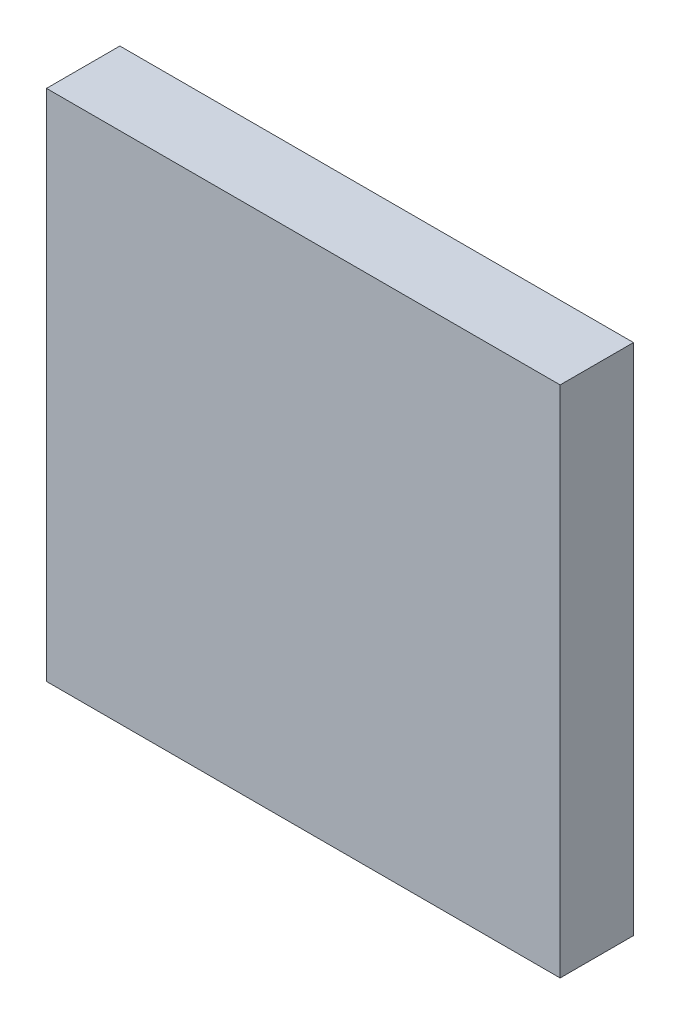
SolidWorks part; units mm, degrees
ref_plane "Спереди" through (0, 0, 0) normal (0, 0, 1) x (1, 0, 0)
ref_plane "Сверху" through (0, 0, 0) normal (0, 1, 0) x (1, 0, 0)
ref_plane "Справа" through (0, 0, 0) normal (1, 0, 0) x (0, 0, -1)
sketch "Эскиз5" plane through (0, 0, 0) normal (0, 0, 1) x (1, 0, 0)
  line L1 (-35, -35) -> (35, -35)
  line L2 (-35, -35) -> (-35, 35)
  line L3 (-35, 35) -> (35, 35)
  line L4 (35, -35) -> (35, 35)
  line L5 (-35, -35) -> (35, 35) construction
  line L6 (-35, 35) -> (35, -35) construction
  point P0 (0, 0)
extrude "Бобышка-Вытянуть2" add sketch "Эскиз5" along normal blind 10 contours L2 L3 L4 L1
sketch "Эскиз9" plane through (0, 0, 10) normal (0, 0, 1) x (1, 0, 0)
  line L0 (-15.9693, -2.4457) -> (-15.2752, -2.3914)
  line L1 (-14.1689, -1.194) -> (-14.17, 0.0011)
  line L2 (-15.1833, 1.1854) -> (-16.1735, 1.3414)
  line L3 (-7.5117, 15.2981) -> (-6.354, 13.3333)
  line L4 (-4.52, 14.0613) -> (-5.009, 16.2935)
  line L5 (5.8666, 15.0526) -> (5.5666, 14.4244)
  line L6 (6.0505, 12.8676) -> (7.0859, 12.271)
  line L7 (8.6182, 12.5564) -> (9.2484, 13.336)
  line L8 (16.9601, -1.13) -> (14.724, -1.1639)
  line L9 (14.4375, -3.1163) -> (16.5652, -3.7935)
  line L10 (10.1027, -12.6069) -> (9.7086, -12.0331)
  line L11 (8.1185, -11.6737) -> (7.0841, -12.2721)
  line L12 (6.5651, -13.7418) -> (6.9251, -14.6773)
  line L13 (-9.4469, -14.0923) -> (-8.37, -12.1694)
  line L14 (-9.9175, -10.9451) -> (-11.5447, -12.4356)
  line L15 (-30, -30) -> (30, -30)
  line L16 (30, -30) -> (30, 30)
  line L17 (30, 30) -> (-30, 30)
  line L18 (-30, 30) -> (-30, -30)
  ellipse E0 centre (-0.0001, 0.0435) end of major axis (-0.0001, 12.5436) minor radius 12.5001
  spline S0 degree 3 poles (3, -26) (3, -24.3431) (1.6569, -23) (0, -23) knots 0 0 0 0 0.2 0.2 0.2 0.2
  spline S1 degree 3 poles (0, -23) (-1.6568, -23) (-3, -24.3431) (-3, -26) knots 0.2 0.2 0.2 0.2 0.4 0.4 0.4 0.4
  spline S2 degree 3 poles (-3, -26) (-3, -27.6568) (-1.6569, -29) (0, -29) knots 0.4 0.4 0.4 0.4 0.6 0.6 0.6 0.6
  spline S3 degree 3 poles (0, -29) (1.6568, -29) (3, -27.6569) (3, -26) knots 0.6 0.6 0.6 0.6 1 1 1 1
  spline S4 degree 3 poles (-23, 0) (-23, 1.6569) (-24.3431, 3) (-26, 3) knots 0 0 0 0 0.2 0.2 0.2 0.2
  spline S5 degree 3 poles (-26, 3) (-27.6568, 3) (-29, 1.6569) (-29, 0) knots 0.2 0.2 0.2 0.2 0.4 0.4 0.4 0.4
  spline S6 degree 3 poles (-29, 0) (-29, -1.6568) (-27.6569, -3) (-26, -3) knots 0.4 0.4 0.4 0.4 0.6 0.6 0.6 0.6
  spline S7 degree 3 poles (-26, -3) (-24.3432, -3) (-23, -1.6569) (-23, 0) knots 0.6 0.6 0.6 0.6 1 1 1 1
  spline S8 degree 3 poles (29, 0) (29, 1.6569) (27.6569, 3) (26, 3) knots 0 0 0 0 0.2 0.2 0.2 0.2
  spline S9 degree 3 poles (26, 3) (24.3432, 3) (23, 1.6569) (23, 0) knots 0.2 0.2 0.2 0.2 0.4 0.4 0.4 0.4
  spline S10 degree 3 poles (23, 0) (23, -1.6568) (24.3431, -3) (26, -3) knots 0.4 0.4 0.4 0.4 0.6 0.6 0.6 0.6
  spline S11 degree 3 poles (26, -3) (27.6568, -3) (29, -1.6569) (29, 0) knots 0.6 0.6 0.6 0.6 1 1 1 1
  spline S12 degree 3 poles (3, 26) (3, 27.6569) (1.6569, 29) (0, 29) knots 0 0 0 0 0.2 0.2 0.2 0.2
  spline S13 degree 3 poles (0, 29) (-1.6568, 29) (-3, 27.6569) (-3, 26) knots 0.2 0.2 0.2 0.2 0.4 0.4 0.4 0.4
  spline S14 degree 3 poles (-3, 26) (-3, 24.3432) (-1.6569, 23) (0, 23) knots 0.4 0.4 0.4 0.4 0.6 0.6 0.6 0.6
  spline S15 degree 3 poles (0, 23) (1.6568, 23) (3, 24.3431) (3, 26) knots 0.6 0.6 0.6 0.6 1 1 1 1
  spline S16 degree 3 poles (-16.7485, -2.8866) (-16.7849, -2.7489) (-16.7119, -2.6575) (-16.5914, -2.5899) knots 0 0 0 0 0.021277 0.021277 0.021277 0.021277
  spline S17 degree 3 poles (-16.5914, -2.5899) (-16.4679, -2.5206) (-16.1105, -2.4568) (-15.9693, -2.4457) knots 0.021277 0.021277 0.021277 0.021277 0.042553 0.042553 0.042553 0.042553
  spline S18 degree 3 poles (-15.2752, -2.3914) (-14.6503, -2.3424) (-14.1684, -1.8208) (-14.1689, -1.194) knots 0.06383 0.06383 0.06383 0.06383 0.085106 0.085106 0.085106 0.085106
  spline S19 degree 3 poles (-14.17, 0.0011) (-14.1705, 0.5913) (-14.6002, 1.0936) (-15.1833, 1.1854) knots 0.106383 0.106383 0.106383 0.106383 0.12766 0.12766 0.12766 0.12766
  spline S20 degree 3 poles (-16.1735, 1.3414) (-16.4381, 1.383) (-16.9337, 1.6001) (-16.9034, 1.8662) knots 0.148936 0.148936 0.148936 0.148936 0.170213 0.170213 0.170213 0.170213
  spline S21 degree 3 poles (-16.9034, 1.8662) (-16.2735, 7.7755) (-12.6158, 12.7801) (-7.5117, 15.2981) knots 0.170213 0.170213 0.170213 0.170213 0.191489 0.191489 0.191489 0.191489
  spline S22 degree 3 poles (-6.354, 13.3333) (-6.1017, 12.914) (-5.5831, 12.7389) (-5.1282, 12.9194) knots 0.212766 0.212766 0.212766 0.212766 0.234043 0.234043 0.234043 0.234043
  spline S23 degree 3 poles (-5.1282, 12.9194) (-4.6734, 13.1) (-4.416, 13.5832) (-4.52, 14.0613) knots 0.234043 0.234043 0.234043 0.234043 0.255319 0.255319 0.255319 0.255319
  spline S24 degree 3 poles (-5.009, 16.2935) (-3.4256, 16.781) (-1.7434, 17.0434) (0, 17.0434) knots 0.276596 0.276596 0.276596 0.276596 0.297872 0.297872 0.297872 0.297872
  spline S25 degree 3 poles (0, 17.0434) (2.06, 17.0434) (4.0345, 16.6769) (5.8617, 16.0058) knots 0.297872 0.297872 0.297872 0.297872 0.319149 0.319149 0.319149 0.319149
  spline S26 degree 3 poles (5.8617, 16.0058) (5.9953, 15.9584) (6.0613, 15.8415) (6.1155, 15.7106) knots 0.319149 0.319149 0.319149 0.319149 0.340426 0.340426 0.340426 0.340426
  spline S27 degree 3 poles (6.1155, 15.7106) (6.1697, 15.5797) (5.9276, 15.1805) (5.8666, 15.0526) knots 0.340426 0.340426 0.340426 0.340426 0.361702 0.361702 0.361702 0.361702
  spline S28 degree 3 poles (5.5666, 14.4244) (5.2966, 13.8588) (5.5074, 13.1805) (6.0505, 12.8676) knots 0.382979 0.382979 0.382979 0.382979 0.404255 0.404255 0.404255 0.404255
  spline S29 degree 3 poles (7.0859, 12.271) (7.5974, 11.9764) (8.2472, 12.0974) (8.6182, 12.5564) knots 0.425532 0.425532 0.425532 0.425532 0.446809 0.446809 0.446809 0.446809
  spline S30 degree 3 poles (9.2484, 13.336) (9.4155, 13.5426) (9.7733, 13.9496) (9.9892, 13.8005) knots 0.468085 0.468085 0.468085 0.468085 0.489362 0.489362 0.489362 0.489362
  spline S31 degree 3 poles (9.9892, 13.8005) (9.9897, 13.8002) (9.9901, 13.7998) (9.9906, 13.7995) knots 0.489362 0.489362 0.489362 0.489362 0.510638 0.510638 0.510638 0.510638
  spline S32 degree 3 poles (9.9906, 13.7995) (14.2385, 10.7091) (17, 5.6988) (17, 0.0434) knots 0.510638 0.510638 0.510638 0.510638 0.531915 0.531915 0.531915 0.531915
  spline S33 degree 3 poles (17, 0.0434) (17, -0.351) (16.9865, -0.7423) (16.9601, -1.13) knots 0.531915 0.531915 0.531915 0.531915 0.553191 0.553191 0.553191 0.553191
  spline S34 degree 3 poles (14.724, -1.1639) (14.2347, -1.1728) (13.8237, -1.5344) (13.7527, -2.0186) knots 0.574468 0.574468 0.574468 0.574468 0.595745 0.595745 0.595745 0.595745
  spline S35 degree 3 poles (13.7527, -2.0186) (13.6816, -2.5027) (13.9714, -2.9672) (14.4375, -3.1163) knots 0.595745 0.595745 0.595745 0.595745 0.617021 0.617021 0.617021 0.617021
  spline S36 degree 3 poles (16.5652, -3.7935) (15.7442, -7.3523) (13.8058, -10.484) (11.1395, -12.7989) knots 0.638298 0.638298 0.638298 0.638298 0.659574 0.659574 0.659574 0.659574
  spline S37 degree 3 poles (11.1395, -12.7989) (11.0317, -12.8908) (10.5897, -12.8381) (10.4494, -12.8196) knots 0.659574 0.659574 0.659574 0.659574 0.680851 0.680851 0.680851 0.680851
  spline S38 degree 3 poles (10.4494, -12.8196) (10.3089, -12.8011) (10.1829, -12.7237) (10.1027, -12.6069) knots 0.680851 0.680851 0.680851 0.680851 0.702128 0.702128 0.702128 0.702128
  spline S39 degree 3 poles (9.7086, -12.0331) (9.3538, -11.5163) (8.661, -11.3598) (8.1185, -11.6737) knots 0.723404 0.723404 0.723404 0.723404 0.744681 0.744681 0.744681 0.744681
  spline S40 degree 3 poles (7.0841, -12.2721) (6.5732, -12.5677) (6.3531, -13.1909) (6.5651, -13.7418) knots 0.765957 0.765957 0.765957 0.765957 0.787234 0.787234 0.787234 0.787234
  spline S41 degree 3 poles (6.9251, -14.6773) (7.021, -14.9265) (6.922, -15.4856) (6.6778, -15.5949) knots 0.808511 0.808511 0.808511 0.808511 0.829787 0.829787 0.829787 0.829787
  spline S42 degree 3 poles (6.6778, -15.5949) (4.6278, -16.4714) (2.3705, -16.9566) (0, -16.9566) knots 0.829787 0.829787 0.829787 0.829787 0.851064 0.851064 0.851064 0.851064
  spline S43 degree 3 poles (0, -16.9566) (-3.4958, -16.9566) (-6.7452, -15.9014) (-9.4469, -14.0923) knots 0.851064 0.851064 0.851064 0.851064 0.87234 0.87234 0.87234 0.87234
  spline S44 degree 3 poles (-8.37, -12.1694) (-8.133, -11.7413) (-8.2407, -11.2045) (-8.6244, -10.9009) knots 0.893617 0.893617 0.893617 0.893617 0.914894 0.914894 0.914894 0.914894
  spline S45 degree 3 poles (-8.6244, -10.9009) (-9.0082, -10.5972) (-9.5554, -10.6159) (-9.9175, -10.9451) knots 0.914894 0.914894 0.914894 0.914894 0.93617 0.93617 0.93617 0.93617
  spline S46 degree 3 poles (-11.5447, -12.4356) (-14.22, -9.9595) (-16.0977, -6.6335) (-16.7485, -2.8866) knots 0.957447 0.957447 0.957447 0.957447 1 1 1 1
sketch "Эскиз13" plane through (0, 0, 10) normal (0, 0, 1) x (1, 0, 0)
  line L0 (-8.5, 3.8388) -> (-8.5, -2.9703)
  line L1 (8.5, -2.9278) -> (8.5, 3.8388)
  spline S0 degree 3 poles (-3.7602, -6.2881) (-4.1456, -5.7125) (-4.7609, -5.3316) (-5.448, -5.2431) knots 0 0 0 0 0.333333 0.333333 0.333333 0.333333
  spline S1 degree 3 poles (-5.448, -5.2431) (-6.135, -5.1547) (-6.8268, -5.3675) (-7.3454, -5.8267) knots 0.333333 0.333333 0.333333 0.333333 1 1 1 1
  spline S2 degree 3 poles (-8.2703, 4.2595) (-8.4134, 4.1675) (-8.5, 4.009) (-8.5, 3.8388) knots 0 0 0 0 1 1 1 1
  spline S3 degree 3 poles (8.2703, 4.2595) (3.2319, 7.4966) (-3.2319, 7.4966) (-8.2703, 4.2595) knots 0 0 0 0 1 1 1 1
  spline S4 degree 3 poles (8.5, 3.8388) (8.5, 4.009) (8.4134, 4.1675) (8.2703, 4.2595) knots 0 0 0 0 1 1 1 1
  spline S5 degree 3 poles (-8.9672, -4.0581) (-8.6689, -3.7749) (-8.5, -3.3816) (-8.5, -2.9703) knots 0 0 0 0 1 1 1 1
  spline S6 degree 3 poles (-8.9672, -4.0581) (-9.4419, -4.5088) (-9.4678, -5.2568) (-9.0253, -5.7393) knots 0 0 0 0 0.333333 0.333333 0.333333 0.333333
  spline S7 degree 3 poles (-9.0253, -5.7393) (-8.5829, -6.2218) (-7.8355, -6.2607) (-7.3454, -5.8267) knots 0.333333 0.333333 0.333333 0.333333 1 1 1 1
  spline S8 degree 3 poles (8.5, -2.9278) (8.5, -3.3579) (8.6732, -3.77) (8.9805, -4.0709) knots 0 0 0 0 1 1 1 1
  spline S9 degree 3 poles (7.6987, -6.0438) (6.4648, -5.5547) (5.0779, -5.6352) (3.9089, -6.2639) knots 0 0 0 0 1 1 1 1
  spline S10 degree 3 poles (7.6987, -6.0438) (8.2299, -6.2544) (8.8358, -6.0612) (9.1472, -5.5821) knots 0 0 0 0 0.333333 0.333333 0.333333 0.333333
  spline S11 degree 3 poles (9.1472, -5.5821) (9.4585, -5.1029) (9.3888, -4.4707) (8.9805, -4.0709) knots 0.333333 0.333333 0.333333 0.333333 1 1 1 1
  spline S12 degree 3 poles (3.1792, -6.3186) (1.2825, -5.6394) (-0.8063, -5.741) (-2.6281, -6.6012) knots 0 0 0 0 1 1 1 1
  spline S13 degree 3 poles (-3.7602, -6.2881) (-3.5123, -6.6582) (-3.0309, -6.7914) (-2.6281, -6.6012) knots 0 0 0 0 1 1 1 1
  spline S14 degree 3 poles (3.1792, -6.3186) (3.4192, -6.4045) (3.6844, -6.3847) (3.9089, -6.2639) knots 0 0 0 0 1 1 1 1
sketch "Эскиз15" plane through (0, 0, 10) normal (0, 0, 1) x (1, 0, 0)
  line L0 (-8.5, 3.8389) -> (-8.5, -2.9702)
  line L1 (8.5, -2.9277) -> (8.5, 3.8389)
  line L2 (-12.5, -12.5) -> (12.5, -12.5)
  line L3 (12.5, -12.5) -> (12.5, 12.5)
  line L4 (12.5, 12.5) -> (-12.5, 12.5)
  line L5 (-12.5, 12.5) -> (-12.5, -12.5)
  spline S0 degree 3 poles (8, 2.6874) (8, 2.9636) (7.7761, 3.1874) (7.5, 3.1874) knots 0 0 0 0 0.2 0.2 0.2 0.2
  spline S1 degree 3 poles (7.5, 3.1874) (7.2239, 3.1874) (7, 2.9636) (7, 2.6874) knots 0.2 0.2 0.2 0.2 0.4 0.4 0.4 0.4
  spline S2 degree 3 poles (7, 2.6874) (7, 2.4113) (7.2239, 2.1874) (7.5, 2.1874) knots 0.4 0.4 0.4 0.4 0.6 0.6 0.6 0.6
  spline S3 degree 3 poles (7.5, 2.1874) (7.7761, 2.1874) (8, 2.4113) (8, 2.6874) knots 0.6 0.6 0.6 0.6 1 1 1 1
  spline S4 degree 3 poles (-4.6079, 1.1218) (-4.6079, 1.6188) (-5.0108, 2.0218) (-5.5079, 2.0218) knots 0 0 0 0 0.2 0.2 0.2 0.2
  spline S5 degree 3 poles (-5.5079, 2.0218) (-6.0049, 2.0218) (-6.4079, 1.6188) (-6.4079, 1.1218) knots 0.2 0.2 0.2 0.2 0.4 0.4 0.4 0.4
  spline S6 degree 3 poles (-6.4079, 1.1218) (-6.4079, 0.6247) (-6.0049, 0.2218) (-5.5079, 0.2218) knots 0.4 0.4 0.4 0.4 0.6 0.6 0.6 0.6
  spline S7 degree 3 poles (-5.5079, 0.2218) (-5.0108, 0.2218) (-4.6079, 0.6247) (-4.6079, 1.1218) knots 0.6 0.6 0.6 0.6 1 1 1 1
  spline S8 degree 3 poles (7.0549, -0.2908) (7.0549, 0.2063) (6.652, 0.6092) (6.1549, 0.6092) knots 0 0 0 0 0.2 0.2 0.2 0.2
  spline S9 degree 3 poles (6.1549, 0.6092) (5.6579, 0.6092) (5.2549, 0.2063) (5.2549, -0.2908) knots 0.2 0.2 0.2 0.2 0.4 0.4 0.4 0.4
  spline S10 degree 3 poles (5.2549, -0.2908) (5.2549, -0.7878) (5.6579, -1.1908) (6.1549, -1.1908) knots 0.4 0.4 0.4 0.4 0.6 0.6 0.6 0.6
  spline S11 degree 3 poles (6.1549, -1.1908) (6.652, -1.1908) (7.0549, -0.7878) (7.0549, -0.2908) knots 0.6 0.6 0.6 0.6 1 1 1 1
  spline S12 degree 3 poles (-7, 2.6874) (-7, 2.9636) (-7.2239, 3.1874) (-7.5, 3.1874) knots 0 0 0 0 0.2 0.2 0.2 0.2
  spline S13 degree 3 poles (-7.5, 3.1874) (-7.7761, 3.1874) (-8, 2.9636) (-8, 2.6874) knots 0.2 0.2 0.2 0.2 0.4 0.4 0.4 0.4
  spline S14 degree 3 poles (-8, 2.6874) (-8, 2.4113) (-7.7761, 2.1874) (-7.5, 2.1874) knots 0.4 0.4 0.4 0.4 0.6 0.6 0.6 0.6
  spline S15 degree 3 poles (-7.5, 2.1874) (-7.2239, 2.1874) (-7, 2.4113) (-7, 2.6874) knots 0.6 0.6 0.6 0.6 1 1 1 1
  spline S16 degree 3 poles (-7.5909, -4.9282) (-7.5909, -4.6244) (-7.8371, -4.3782) (-8.1409, -4.3782) knots 0 0 0 0 0.2 0.2 0.2 0.2
  spline S17 degree 3 poles (-8.1409, -4.3782) (-8.4447, -4.3782) (-8.6909, -4.6244) (-8.6909, -4.9282) knots 0.2 0.2 0.2 0.2 0.4 0.4 0.4 0.4
  spline S18 degree 3 poles (-8.6909, -4.9282) (-8.6909, -5.2319) (-8.4447, -5.4782) (-8.1409, -5.4782) knots 0.4 0.4 0.4 0.4 0.6 0.6 0.6 0.6
  spline S19 degree 3 poles (-8.1409, -5.4782) (-7.8371, -5.4782) (-7.5909, -5.2319) (-7.5909, -4.9282) knots 0.6 0.6 0.6 0.6 1 1 1 1
  spline S20 degree 3 poles (8.6909, -4.9282) (8.6909, -4.6244) (8.4447, -4.3782) (8.1409, -4.3782) knots 0 0 0 0 0.2 0.2 0.2 0.2
  spline S21 degree 3 poles (8.1409, -4.3782) (7.8371, -4.3782) (7.5909, -4.6244) (7.5909, -4.9282) knots 0.2 0.2 0.2 0.2 0.4 0.4 0.4 0.4
  spline S22 degree 3 poles (7.5909, -4.9282) (7.5909, -5.2319) (7.8371, -5.4782) (8.1409, -5.4782) knots 0.4 0.4 0.4 0.4 0.6 0.6 0.6 0.6
  spline S23 degree 3 poles (8.1409, -5.4782) (8.4447, -5.4782) (8.6909, -5.2319) (8.6909, -4.9282) knots 0.6 0.6 0.6 0.6 1 1 1 1
  spline S24 degree 3 poles (3.9826, -5.4712) (3.9826, -5.195) (3.7587, -4.9712) (3.4826, -4.9712) knots 0 0 0 0 0.2 0.2 0.2 0.2
  spline S25 degree 3 poles (3.4826, -4.9712) (3.2064, -4.9712) (2.9826, -5.195) (2.9826, -5.4712) knots 0.2 0.2 0.2 0.2 0.4 0.4 0.4 0.4
  spline S26 degree 3 poles (2.9826, -5.4712) (2.9826, -5.7473) (3.2064, -5.9712) (3.4826, -5.9712) knots 0.4 0.4 0.4 0.4 0.6 0.6 0.6 0.6
  spline S27 degree 3 poles (3.4826, -5.9712) (3.7587, -5.9712) (3.9826, -5.7473) (3.9826, -5.4712) knots 0.6 0.6 0.6 0.6 1 1 1 1
  spline S28 degree 3 poles (-2.5123, -5.7872) (-2.5123, -5.5111) (-2.7362, -5.2872) (-3.0123, -5.2872) knots 0 0 0 0 0.2 0.2 0.2 0.2
  spline S29 degree 3 poles (-3.0123, -5.2872) (-3.2885, -5.2872) (-3.5123, -5.5111) (-3.5123, -5.7872) knots 0.2 0.2 0.2 0.2 0.4 0.4 0.4 0.4
  spline S30 degree 3 poles (-3.5123, -5.7872) (-3.5123, -6.0634) (-3.2885, -6.2872) (-3.0123, -6.2872) knots 0.4 0.4 0.4 0.4 0.6 0.6 0.6 0.6
  spline S31 degree 3 poles (-3.0123, -6.2872) (-2.7362, -6.2872) (-2.5123, -6.0634) (-2.5123, -5.7872) knots 0.6 0.6 0.6 0.6 1 1 1 1
  spline S32 degree 3 poles (6.6049, -0.2908) (6.6049, -0.0422) (6.4034, 0.1592) (6.1549, 0.1592) knots 0 0 0 0 0.2 0.2 0.2 0.2
  spline S33 degree 3 poles (6.1549, 0.1592) (5.9064, 0.1592) (5.7049, -0.0422) (5.7049, -0.2908) knots 0.2 0.2 0.2 0.2 0.4 0.4 0.4 0.4
  spline S34 degree 3 poles (5.7049, -0.2908) (5.7049, -0.5393) (5.9064, -0.7408) (6.1549, -0.7408) knots 0.4 0.4 0.4 0.4 0.6 0.6 0.6 0.6
  spline S35 degree 3 poles (6.1549, -0.7408) (6.4034, -0.7408) (6.6049, -0.5393) (6.6049, -0.2908) knots 0.6 0.6 0.6 0.6 1 1 1 1
  spline S36 degree 3 poles (-5.0579, 1.1218) (-5.0579, 1.3703) (-5.2594, 1.5718) (-5.5079, 1.5718) knots 0 0 0 0 0.2 0.2 0.2 0.2
  spline S37 degree 3 poles (-5.5079, 1.5718) (-5.7564, 1.5718) (-5.9579, 1.3703) (-5.9579, 1.1218) knots 0.2 0.2 0.2 0.2 0.4 0.4 0.4 0.4
  spline S38 degree 3 poles (-5.9579, 1.1218) (-5.9579, 0.8733) (-5.7564, 0.6718) (-5.5079, 0.6718) knots 0.4 0.4 0.4 0.4 0.6 0.6 0.6 0.6
  spline S39 degree 3 poles (-5.5079, 0.6718) (-5.2594, 0.6718) (-5.0579, 0.8733) (-5.0579, 1.1218) knots 0.6 0.6 0.6 0.6 1 1 1 1
  spline S40 degree 3 poles (5.7898, -5.6368) (5.8728, -5.6949) (5.9715, -5.7264) (6.0728, -5.7271) knots 0 0 0 0 1 1 1 1
  spline S41 degree 3 poles (-5.4083, -5.2485) (-5.2964, -5.2648) (-5.1822, -5.2427) (-5.0845, -5.1857) knots 0 0 0 0 1 1 1 1
  spline S42 degree 3 poles (-3.7602, -6.288) (-4.1456, -5.7124) (-4.7609, -5.3315) (-5.448, -5.243) knots 0 0 0 0 0.333333 0.333333 0.333333 0.333333
  spline S43 degree 3 poles (-5.448, -5.243) (-6.135, -5.1546) (-6.8268, -5.3674) (-7.3454, -5.8266) knots 0.333333 0.333333 0.333333 0.333333 1 1 1 1
  spline S44 degree 3 poles (-8.2703, 4.2596) (-8.4134, 4.1676) (-8.5, 4.0091) (-8.5, 3.8389) knots 0 0 0 0 1 1 1 1
  spline S45 degree 3 poles (8.2703, 4.2596) (3.2319, 7.4967) (-3.2319, 7.4967) (-8.2703, 4.2596) knots 0 0 0 0 1 1 1 1
  spline S46 degree 3 poles (8.5, 3.8389) (8.5, 4.0091) (8.4134, 4.1676) (8.2703, 4.2596) knots 0 0 0 0 1 1 1 1
  spline S47 degree 3 poles (5.7898, -5.6368) (2.563, -3.3793) (-1.6818, -3.2032) (-5.0845, -5.1857) knots 0 0 0 0 1 1 1 1
  spline S48 degree 3 poles (-8.9672, -4.058) (-8.6689, -3.7748) (-8.5, -3.3815) (-8.5, -2.9702) knots 0 0 0 0 1 1 1 1
  spline S49 degree 3 poles (-8.9672, -4.058) (-9.4419, -4.5087) (-9.4678, -5.2567) (-9.0253, -5.7392) knots 0 0 0 0 0.333333 0.333333 0.333333 0.333333
  spline S50 degree 3 poles (-9.0253, -5.7392) (-8.5829, -6.2217) (-7.8355, -6.2606) (-7.3454, -5.8266) knots 0.333333 0.333333 0.333333 0.333333 1 1 1 1
  spline S51 degree 3 poles (8.5, -2.9277) (8.5, -3.3578) (8.6732, -3.7699) (8.9805, -4.0708) knots 0 0 0 0 1 1 1 1
  spline S52 degree 3 poles (7.6987, -6.0437) (6.4648, -5.5546) (5.0779, -5.6351) (3.9089, -6.2638) knots 0 0 0 0 1 1 1 1
  spline S53 degree 3 poles (7.6987, -6.0437) (8.2299, -6.2543) (8.8358, -6.0611) (9.1472, -5.582) knots 0 0 0 0 0.333333 0.333333 0.333333 0.333333
  spline S54 degree 3 poles (9.1472, -5.582) (9.4585, -5.1028) (9.3888, -4.4706) (8.9805, -4.0708) knots 0.333333 0.333333 0.333333 0.333333 1 1 1 1
  spline S55 degree 3 poles (3.1792, -6.3185) (1.2825, -5.6393) (-0.8063, -5.7409) (-2.6281, -6.6011) knots 0 0 0 0 1 1 1 1
  spline S56 degree 3 poles (-3.7602, -6.288) (-3.5123, -6.6581) (-3.0309, -6.7913) (-2.6281, -6.6011) knots 0 0 0 0 1 1 1 1
  spline S57 degree 3 poles (3.1792, -6.3185) (3.4192, -6.4044) (3.6844, -6.3846) (3.9089, -6.2638) knots 0 0 0 0 1 1 1 1
sketch "обнижение под перлаж" plane through (0, 0, 10) normal (0, 0, 1) x (1, 0, 0)
  ellipse E0 centre (0, -7.2674) end of major axis (6.1105, -7.2674) minor radius 3.5988
sketch "Платина" plane through (0, 0, 10) normal (0, 0, 1) x (1, 0, 0)
  line L0 (12.3202, 9.8119) -> (12.2227, 9.9331)
  line L1 (2.5, -10.2511) -> (2.5, -15.1183)
  line L2 (7.4454, 12.0481) -> (8.1376, 12.9446)
  line L3 (11.9295, 9) -> (9.0138, 9)
  line L4 (8.1828, -12.8608) -> (5.8429, -9.208)
  line L5 (6.6238, -9) -> (11.9295, -9)
  line L6 (2.5, 15.1183) -> (2.5, 13.3766)
  line L7 (-0.6426, 13.86) -> (0.5426, 13.86)
  line L8 (1.1426, 14.46) -> (1.1426, 15.1613)
  line L9 (-6.3695, 9.5643) -> (-6.5795, 9.5485)
  line L10 (-0.9887, -9.3998) -> (-1.9416, -7.3197)
  line L11 (-0.0126, 4.7745) -> (-0.0058, 4.7671)
  line L12 (-5.5717, -10.8712) -> (-5.5074, -10.8831)
  line L13 (-2.7325, 15.5111) -> (-2.8513, 15.4898)
  line L14 (-1.1426, 14.46) -> (-1.1426, 15.1613)
  circle A0 centre (10.4255, 9.7146) radius 0.3
  circle A1 centre (10.4255, 9.7146) radius 0.35
  circle A2 centre (-9.7185, -10.4218) radius 0.4
  circle A3 centre (-9.7185, -10.4218) radius 0.6
  circle A4 centre (-5.4971, -13.8489) radius 0.4
  circle A5 centre (-8.9636, -11.0777) radius 0.35
  circle A6 centre (9.7185, 10.4218) radius 0.6
  circle A7 centre (-8.9636, -11.0777) radius 0.3
  circle A8 centre (9.7185, 10.4218) radius 0.4
  circle A9 centre (-3.1235, -7.8611) radius 0.55
  circle A10 centre (-3.1235, -7.8611) radius 0.5
  circle A11 centre (-5.0761, 0) radius 1.1
  circle A12 centre (-13.4764, 3.3335) radius 0.45
  circle A13 centre (-13.7094, -2.1616) radius 0.45
  circle A14 centre (-13.8634, 0.5974) radius 0.45
  circle A15 centre (-13.8634, 0.5974) radius 0.3
  circle A16 centre (-13.7094, -2.1616) radius 0.4
  circle A17 centre (-13.4764, 3.3335) radius 0.4
  circle A18 centre (-9.2449, 11.6851) radius 0.4
  circle A19 centre (11.3, 7.5) radius 0.55
  circle A20 centre (11.3, -7.5) radius 0.55
  circle A21 centre (9.7344, 5.5079) radius 0.45
  circle A22 centre (8.3218, -6.1549) radius 0.45
  circle A23 centre (14.7421, 2.1638) radius 0.4
  circle A24 centre (11.3, -7.5) radius 0.5
  circle A25 centre (11.3, 7.5) radius 0.5
  circle A26 centre (9.7344, 5.5079) radius 0.3
  circle A27 centre (8.3218, -6.1549) radius 0.3
  circle A28 centre (-5.0761, 0) radius 0.45
  circle A29 centre (-5.0761, 0) radius 0.4
  circle A30 centre (3.78, -11.6) radius 0.45
  circle A31 centre (-1.9546, 8.9725) radius 0.45
  circle A32 centre (-3.78, 11.6) radius 0.4
  circle A33 centre (-3.78, 11.6) radius 0.45
  circle A34 centre (-4.7981, 13.3147) radius 0.45
  circle A35 centre (3.78, -11.6) radius 0.4
  circle A36 centre (-1.9546, 8.9725) radius 0.4
  circle A37 centre (-4.7981, 13.3147) radius 0.4
  circle A38 centre (3.6844, 8.1409) radius 0.53
  circle A39 centre (2.8254, 3.0123) radius 0.53
  circle A40 centre (3.1415, -3.4824) radius 0.53
  circle A41 centre (3.6844, -8.1409) radius 0.53
  circle A42 centre (3.1415, -3.4824) radius 0.5
  circle A43 centre (2.8254, 3.0123) radius 0.5
  circle A44 centre (3.6844, -8.1409) radius 0.5
  circle A45 centre (3.6844, 8.1409) radius 0.5
  arc A46 (12.4118, 9.3683) -> (11.799, 10.1292) centre (0, 0) ccw
  arc A47 (2.439, 15.3575) -> (1.2728, 15.4978) centre (0, 0) ccw
  arc A48 (-13.8027, -7.1616) -> (-10.9014, -11.0888) centre (0, 0) ccw
  arc A49 (8.4366, -13.0624) -> (12.4117, -9.3677) centre (0, 0) ccw
  arc A50 (10.1874, 11.7482) -> (8.3636, 13.1093) centre (0, 0) ccw
  arc A51 (12.2227, 9.9331) -> (1.6964, 15.6584) centre (0, 0) ccw
  arc A52 (-9.1597, -12.5659) -> (2.439, -15.3575) centre (0, 0) ccw
  arc A53 (1.5549, -8.6935) -> (0.785, -8.4089) centre (1.071, -8.8191) ccw
  arc A54 (2.5, -10.2511) -> (2.3119, -9.8603) centre (2, -10.2511) ccw
  arc A55 (-9.1597, -12.5659) -> (-10.9014, -11.0888) centre (-11.0926, -13.0796) ccw
  arc A56 (-12.767, -7.0116) -> (-13.7672, -7.0979) centre (-13.233, -7.4492) ccw
  arc A57 (-12.767, -7.0116) -> (-5.5717, -10.8712) centre (-3.084, 2.403) ccw
  arc A58 (-5.3691, -10.9581) -> (-1.8802, -11.4789) centre (-3.1235, -7.8611) ccw
  arc A59 (-1.8802, -11.4789) -> (-0.9887, -9.3998) centre (-2.3763, -10.0355) ccw
  arc A60 (-0.6012, -9.2216) -> (-0.8748, -9.7613) centre (-0.383, -9.6714) ccw
  arc A61 (-0.6012, -9.2216) -> (0.785, -8.4089) centre (-5.0761, 0) ccw
  arc A62 (-5.3691, -10.9581) -> (-5.5717, -10.8712) centre (-5.6626, -11.3629) ccw
  arc A63 (2.439, -15.3575) -> (2.5, -15.1183) centre (2, -15.1183) ccw
  arc A64 (-13.7672, -7.0979) -> (-13.8027, -7.1616) centre (-13.3494, -7.3726) ccw
  arc A65 (10.1874, 11.7482) -> (11.799, 10.1292) centre (12.1567, 12.097) ccw
  arc A66 (6.0738, 3.7488) -> (7.4632, 11.4151) centre (3.6844, 8.1409) ccw
  arc A67 (7.4454, 12.0481) -> (7.4632, 11.4151) centre (7.8411, 11.7425) ccw
  arc A68 (8.5293, 9.3764) -> (9.0138, 9) centre (9.0138, 9.5) ccw
  arc A69 (8.3636, 13.1093) -> (8.1376, 12.9446) centre (8.5334, 12.639) ccw
  arc A70 (11.9295, 9) -> (12.4118, 9.3683) centre (11.9295, 9.5) ccw
  arc A71 (6.6238, -9) -> (6.2027, -9.7697) centre (6.6238, -9.5) ccw
  arc A72 (12.4117, -9.3677) -> (11.9295, -9) centre (11.9295, -9.5) ccw
  arc A73 (8.1828, -12.8608) -> (8.4366, -13.0624) centre (8.6038, -12.5912) ccw
  arc A74 (2.1531, 12.9006) -> (2.5, 13.3766) centre (2, 13.3766) ccw
  arc A75 (-0.6426, 13.86) -> (-0.8081, 13.1169) centre (-0.6426, 13.47) ccw
  arc A76 (2.1531, 12.9006) -> (-0.7378, 10.4741) centre (3.6844, 8.1409) ccw
  arc A77 (0.5671, 12.4555) -> (1.117, 12.4314) centre (0.8603, 12.8605) ccw
  arc A78 (0.5426, 13.86) -> (1.1426, 14.46) centre (0.5426, 14.46) ccw
  arc A79 (1.2728, 15.4978) -> (1.1426, 15.1613) centre (1.6426, 15.1613) ccw
  arc A80 (2.5, 15.1183) -> (2.439, 15.3575) centre (2, 15.1183) ccw
  arc A81 (-7.0932, 10.1997) -> (-6.5795, 9.5485) centre (-6.617, 10.0471) ccw
  arc A82 (-6.0923, 10.1429) -> (-6.3468, 10.7247) centre (-6.5734, 10.279) ccw
  arc A83 (-6.3695, 9.5643) -> (-6.1876, 9.7286) centre (-6.3845, 9.7637) ccw
  arc A84 (-5.612, 11.2339) -> (-0.5457, 4.9099) centre (-1.9546, 8.9725) ccw
  arc A85 (-6.3468, 10.7247) -> (-7.0716, 10.2777) centre (-6.4873, 10.1414) ccw
  arc A86 (-7.8732, 9.5197) -> (-7.0716, 10.2777) centre (-8.0455, 10.5047) ccw
  arc A87 (0.4324, -5.6985) -> (-0.2788, -5.6343) centre (0.0454, -6.015) ccw
  arc A88 (1.6904, -7.2114) -> (1.4753, -6.5604) centre (1.2372, -7.0001) ccw
  arc A89 (-1.9416, -7.3197) -> (-1.9622, -7.2769) centre (-3.1235, -7.8611) ccw
  arc A90 (-1.7409, -6.6058) -> (-1.9622, -7.2769) centre (-1.5156, -7.0521) ccw
  arc A91 (-0.2801, -2.7456) -> (1.4753, -6.5604) centre (3.1415, -3.4824) ccw
  arc A92 (-2.5221, -6.9453) -> (-0.2788, -5.6343) centre (-5.0761, 0) ccw
  arc A93 (-12.4906, -4.5249) -> (-11.6206, -3.4539) centre (-12.2839, -3.804) ccw
  arc A94 (-13.294, -3.176) -> (-13.4339, -4.0149) centre (-13.1045, -3.6387) ccw
  arc A95 (-13.294, -3.176) -> (-12.6266, -1.9908) centre (-13.7094, -2.1616) ccw
  arc A96 (-12.4086, 3.0694) -> (-12.6266, -1.9908) centre (0, 0) ccw
  arc A97 (-12.4086, 3.0694) -> (-12.9816, 4.3159) centre (-13.4764, 3.3335) ccw
  arc A98 (-13.2216, 4.8947) -> (-12.9816, 4.3159) centre (-12.7656, 4.7446) ccw
  arc A99 (-7.8732, 9.5197) -> (-13.2216, 4.8947) centre (-6.6881, 2.7443) ccw
  arc A100 (-6.5006, 7.2616) -> (-11.6206, -3.4539) centre (-5.0761, 0) ccw
  arc A101 (-13.3852, -4.0569) -> (-11.2448, -4.5599) centre (-11.7995, -2.1148) ccw
  arc A102 (-6.5006, 7.2616) -> (-6.1133, 7.8794) centre (-6.5969, 7.7522) ccw
  arc A103 (-13.4339, -4.0149) -> (-13.3852, -4.0569) centre (-10.4129, -0.5655) ccw
  arc A104 (-1.2717, -8.7821) -> (-2.4697, -8.5503) centre (-1.9535, -9.0945) ccw
  arc A105 (-2.8425, -6.9536) -> (-2.4697, -8.5503) centre (-3.1235, -7.8611) ccw
  arc A106 (-2.8425, -6.9536) -> (-2.5221, -6.9453) centre (-2.6946, -6.476) ccw
  arc A107 (-4.3028, -9.861) -> (-4.6898, -7.9124) centre (-13.084, -10.592) ccw
  arc A108 (-4.6898, -7.9124) -> (-5.6008, -7.2173) centre (-5.6424, -8.2165) ccw
  arc A109 (-10.7557, -4.7208) -> (-11.2448, -4.5599) centre (-11.1341, -5.0475) ccw
  arc A110 (-0.0126, 4.7745) -> (-0.5457, 4.9099) centre (-0.3819, 4.4375) ccw
  arc A111 (0.0824, 4.2272) -> (-0.0058, 4.7671) centre (-0.3748, 4.4297) ccw
  arc A112 (1.0574, 5.436) -> (-0.1603, 2.719) centre (2.8254, 3.0123) ccw
  arc A113 (-0.5383, 2.1847) -> (-0.1603, 2.719) centre (-0.6579, 2.6702) ccw
  arc A114 (-0.5383, 2.1847) -> (-0.6291, -2.1603) centre (0, 0) ccw
  arc A115 (-5.5074, -10.8831) -> (-4.3028, -9.861) centre (-5.2932, -9.9147) ccw
  arc A116 (-10.7557, -4.7208) -> (-5.6008, -7.2173) centre (-5.2873, 0) ccw
  arc A117 (-0.2801, -2.7456) -> (-0.6291, -2.1603) centre (-0.7689, -2.6403) ccw
  arc A118 (-15.296, -2.8563) -> (-15.5588, 0.228) centre (-16.2412, -1.3835) ccw
  arc A119 (-15.7416, 0.514) -> (-15.5588, 0.228) centre (-15.4418, 0.5042) ccw
  arc A120 (-15.5207, 1.1114) -> (-15.7275, 0.8421) centre (-15.4279, 0.8261) ccw
  arc A121 (-15.5207, 1.1114) -> (-14.9936, 4.1616) centre (-16.0619, 2.7756) ccw
  arc A122 (-15.098, 4.4846) -> (-14.9936, 4.1616) centre (-14.8104, 4.3992) ccw
  arc A123 (-15.0279, 4.5471) -> (-15.1077, 4.359) centre (-14.9095, 4.3858) ccw
  arc A124 (-14.6619, 4.639) -> (-12.956, 5.577) centre (-14.4341, 6.2451) ccw
  arc A125 (-13.3852, -4.0569) -> (-15.0699, -3.3705) centre (-15.3458, -6.4583) ccw
  arc A126 (-15.37, -3.2347) -> (-15.0699, -3.3705) centre (-15.0254, -2.8725) ccw
  arc A127 (-15.4285, -3.0519) -> (-15.37, -3.2347) centre (-15.2322, -3.0898) ccw
  arc A128 (-15.296, -2.8563) -> (-15.4279, -3.1692) centre (-15.134, -3.1088) ccw
  arc A129 (-14.6619, 4.639) -> (-15.0279, 4.5471) centre (-14.732, 4.144) ccw
  arc A130 (-5.612, 11.2339) -> (-5.7556, 11.91) centre (-6.0372, 11.4968) ccw
  arc A131 (-6.4878, 13.5014) -> (-7.2138, 14.0008) centre (-6.9848, 13.5564) ccw
  arc A132 (-6.4878, 13.5014) -> (-5.1181, 11.6451) centre (-4.7981, 13.3147) ccw
  arc A133 (5.4708, -6.0947) -> (5.4112, -6.7777) centre (5.8036, -6.4679) ccw
  arc A134 (5.4708, -6.0947) -> (3.9942, -0.0879) centre (3.1415, -3.4824) ccw
  arc A135 (3.9942, 0.2494) -> (3.9942, -0.0879) centre (4.1787, 0.0807) ccw
  arc A136 (3.9942, 0.2494) -> (5.2866, 4.7276) centre (2.8254, 3.0123) ccw
  arc A137 (6.0738, 3.7488) -> (5.8145, 3.2671) centre (6.3127, 3.3096) ccw
  arc A138 (5.7863, -8.7906) -> (5.8429, -9.208) centre (6.264, -8.9383) ccw
  arc A139 (1.6904, -7.2114) -> (5.4112, -6.7777) centre (3.6844, -8.1409) ccw
  arc A140 (-2.8513, 15.4898) -> (-2.9574, 15.1516) centre (-2.8159, 15.2929) ccw
  arc A141 (-2.5522, 15.4522) -> (-2.7325, 15.5111) centre (-2.6971, 15.3143) ccw
  arc A142 (-1.7022, 13.4831) -> (-2.5522, 15.4522) centre (-4.7981, 13.3147) ccw
  arc A143 (-1.9042, 13.2722) -> (-1.7022, 13.4831) centre (-1.9019, 13.4722) ccw
  arc A144 (-2.2017, 13.461) -> (-1.9999, 13.2723) centre (-2.002, 13.4723) ccw
  arc A145 (-2.2017, 13.461) -> (-2.9574, 15.1516) centre (-4.7981, 13.3147) ccw
  arc A146 (0.5671, 12.4555) -> (-2.8467, 13.179) centre (-1.9546, 8.9725) ccw
  arc A147 (-3.0981, 13.3147) -> (-2.8467, 13.179) centre (-2.9059, 13.37) ccw
  arc A148 (-3.1791, 12.7964) -> (-3.616, 14.5364) centre (-4.7981, 13.3147) ccw
  arc A149 (-3.3754, 15.3841) -> (-3.616, 14.5364) centre (-3.2683, 14.8957) ccw
  arc A150 (-2.8513, 15.4898) -> (12.3202, 9.8119) centre (0, 0) ccw
  arc A151 (-1.1426, 15.1613) -> (-1.6964, 15.6584) centre (-1.6426, 15.1613) ccw
  arc A152 (-1.1426, 14.46) -> (-0.5426, 13.86) centre (-0.5426, 14.46) ccw
  arc A153 (-1.6964, 15.6584) -> (-2.7325, 15.5111) centre (0, 0) ccw
  arc A154 (-3.1791, 12.7964) -> (-3.0619, 12.2959) centre (-2.7029, 12.6439) ccw
  arc A155 (-1.3839, 10.2509) -> (-0.7378, 10.4741) centre (-1.18, 10.7075) ccw
  arc A156 (-1.3839, 10.2509) -> (-1.7772, 7.5838) centre (-1.9546, 8.9725) ccw
  arc A157 (-1.2231, 7.1836) -> (-1.7772, 7.5838) centre (-1.7138, 7.0878) ccw
  arc A158 (-4.7348, 11.3027) -> (-5.1181, 11.6451) centre (-5.2122, 11.154) ccw
  arc A159 (-4.7348, 11.3027) -> (-3.0619, 12.2959) centre (-3.78, 11.6) ccw
  arc A160 (-1.2231, 7.1836) -> (-0.0126, 4.7745) centre (3.6844, 8.1409) ccw
  arc A161 (5.0447, 7.5087) -> (2.1924, 7.9864) centre (3.6844, 8.1409) ccw
  arc A162 (1.0574, 5.436) -> (2.1924, 7.9864) centre (-0.5927, 7.6981) ccw
  arc A163 (5.0447, 7.5087) -> (5.2866, 4.7276) centre (7.5838, 6.3285) ccw
  arc A164 (-0.6291, -2.1603) -> (-0.5383, 2.1847) centre (0, 0) ccw
  spline S0 degree 3 poles (11.799, 10.1292) (11.833, 10.1237) (11.8667, 10.1191) (11.9002, 10.1155) knots 0 0 0 0 1 1 1 1
  spline S1 degree 3 poles (12.2227, 9.9331) (12.1797, 9.9867) (12.1265, 10.0297) (12.0148, 10.0901) (11.9565, 10.1078) (11.9002, 10.1155) knots 0 0 0 0 0.5 0.5 1 1 1 1
  spline S2 degree 3 poles (12.4118, 9.3683) (12.4298, 9.4342) (12.4355, 9.5076) (12.409, 9.6619) (12.375, 9.7434) (12.3202, 9.8119) knots 0 0 0 0 0.5 0.5 1 1 1 1
  spline S3 degree 3 poles (2.439, 15.3575) (2.4063, 15.4176) (2.3596, 15.4744) (2.2335, 15.5673) (2.1526, 15.6025) (2.0656, 15.614) knots 0 0 0 0 0.5 0.5 1 1 1 1
  spline S4 degree 3 poles (1.6964, 15.6584) (1.6091, 15.6678) (1.5233, 15.6533) (1.3773, 15.5924) (1.3188, 15.5484) (1.2728, 15.4978) knots 0 0 0 0 0.5 0.5 1 1 1 1
  spline S5 degree 3 poles (-10.9014, -11.0888) (-10.9357, -11.0855) (-10.9696, -11.0831) (-11.0033, -11.0816) knots 0 0 0 0 1 1 1 1
  spline S6 degree 3 poles (-11.341, -10.9291) (-11.2932, -10.9786) (-11.2364, -11.0166) (-11.1197, -11.0667) (-11.0601, -11.0791) (-11.0033, -11.0816) knots 0 0 0 0 0.5 0.5 1 1 1 1
  spline S7 degree 3 poles (-13.8027, -7.1616) (-13.8315, -7.2236) (-13.8495, -7.2949) (-13.8493, -7.4515) (-13.8295, -7.5375) (-13.7871, -7.6144) knots 0 0 0 0 0.5 0.5 1 1 1 1
  spline S8 degree 3 poles (12.3206, -9.8115) (12.3753, -9.7428) (12.4089, -9.6625) (12.4357, -9.5066) (12.4298, -9.4337) (12.4117, -9.3677) knots 0 0 0 0 0.5 0.5 1 1 1 1
  spline S9 degree 3 poles (8.4366, -13.0624) (8.5011, -13.0852) (8.5738, -13.0964) (8.7297, -13.0813) (8.8134, -13.0535) (8.8859, -13.004) knots 0 0 0 0 0.5 0.5 1 1 1 1
  spline S10 degree 3 poles (8.8131, 13.0534) (8.7404, 13.1025) (8.6577, 13.1297) (8.5002, 13.1441) (8.4279, 13.1325) (8.3636, 13.1093) knots 0 0 0 0 0.5 0.5 1 1 1 1
  spline S11 degree 3 poles (10.1721, 11.8491) (10.1651, 11.9055) (10.1481, 11.9636) (10.089, 12.0761) (10.0464, 12.13) (9.9932, 12.1736) knots 0 0 0 0 0.5 0.5 1 1 1 1
  spline S12 degree 3 poles (10.1721, 11.8491) (10.1763, 11.8157) (10.1814, 11.7821) (10.1874, 11.7482) knots 0 0 0 0 1 1 1 1
  spline S13 degree 3 poles (2.0656, -15.614) (2.1526, -15.6025) (2.2325, -15.5679) (2.3599, -15.4742) (2.4063, -15.4176) (2.439, -15.3575) knots 0 0 0 0 0.5 0.5 1 1 1 1
  spline S14 degree 3 poles (-9.136, -12.6652) (-9.1242, -12.7208) (-9.1024, -12.7773) (-9.034, -12.8844) (-8.987, -12.9345) (-8.9303, -12.9735) knots 0 0 0 0 0.5 0.5 1 1 1 1
  spline S15 degree 3 poles (-9.136, -12.6652) (-9.143, -12.6324) (-9.1508, -12.5993) (-9.1597, -12.5659) knots 0 0 0 0 1 1 1 1
sketch "обнижение под платину" plane through (0, 0, 10) normal (0, 0, 1) x (1, 0, 0)
  line L1 (-1.1425, 14.458) -> (-1.1425, 15.1592)
  line L2 (1.1427, 14.458) -> (1.1427, 15.1592)
  line L3 (-0.5425, 13.858) -> (0.5427, 13.858)
  spline S5 degree 3 poles (-1.6963, 15.6563) (-2.043, 15.6188) (-2.3883, 15.5697) (-2.7317, 15.5092) knots 0 0 0 0 1 1 1 1
  spline S6 degree 3 poles (-1.1425, 14.458) (-1.1425, 14.2988) (-1.0792, 14.1462) (-0.9667, 14.0337) knots 0 0 0 0 0.333333 0.333333 0.333333 0.333333
  spline S7 degree 3 poles (-0.9667, 14.0337) (-0.8542, 13.9212) (-0.7016, 13.858) (-0.5425, 13.858) knots 0.333333 0.333333 0.333333 0.333333 1 1 1 1
  spline S8 degree 3 poles (-1.1425, 15.1592) (-1.1425, 15.3012) (-1.2028, 15.4365) (-1.3085, 15.5313) knots 0 0 0 0 0.333333 0.333333 0.333333 0.333333
  spline S9 degree 3 poles (-1.3085, 15.5313) (-1.4142, 15.6262) (-1.5552, 15.6716) (-1.6963, 15.6563) knots 0.333333 0.333333 0.333333 0.333333 1 1 1 1
  spline S10 degree 3 poles (-2.7317, 15.5092) (-9.6978, 14.2443) (-14.9639, 8.4868) (-15.6035, 1.4358) knots 0 0 0 0 0.2 0.2 0.2 0.2
  spline S11 degree 3 poles (-15.6035, 1.4358) (-16.2631, -5.6135) (-12.1379, -12.2364) (-5.5202, -14.7529) knots 0.2 0.2 0.2 0.2 0.4 0.4 0.4 0.4
  spline S12 degree 3 poles (-5.5202, -14.7529) (1.1106, -17.2344) (8.5824, -14.9865) (12.7432, -9.2581) knots 0.4 0.4 0.4 0.4 0.6 0.6 0.6 0.6
  spline S13 degree 3 poles (12.7432, -9.2581) (16.9041, -3.5298) (16.7312, 4.2709) (12.3208, 9.8094) knots 0.6 0.6 0.6 0.6 1 1 1 1
  spline S16 degree 3 poles (1.2729, 15.4958) (1.1891, 15.4037) (1.1427, 15.2837) (1.1427, 15.1592) knots 0 0 0 0 1 1 1 1
  spline S17 degree 3 poles (0.5427, 13.858) (0.874, 13.858) (1.1427, 14.1266) (1.1427, 14.458) knots 0 0 0 0 1 1 1 1
  spline S18 degree 3 poles (12.3208, 9.8094) (9.688, 13.082) (5.87, 15.1832) (1.6965, 15.6563) knots 0 0 0 0 1 1 1 1
  spline S19 degree 3 poles (1.6965, 15.6563) (1.6092, 15.6658) (1.5234, 15.6512) (1.4504, 15.6208) knots 0 0 0 0 0.333333 0.333333 0.333333 0.333333
  spline S20 degree 3 poles (1.4504, 15.6208) (1.3774, 15.5904) (1.3189, 15.5464) (1.2729, 15.4958) knots 0.333333 0.333333 0.333333 0.333333 1 1 1 1
sketch "пипка-остров" plane through (0, 0, 10) normal (0, 0, 1) x (1, 0, 0)
  spline S2 degree 3 poles (-0.6292, -2.1624) (0.2793, -2.427) (1.2563, -2.0948) (1.8153, -1.3313) knots 0 0 0 0 0.25 0.25 0.25 0.25
  spline S3 degree 3 poles (1.8153, -1.3313) (2.3743, -0.5678) (2.3959, 0.4638) (1.8693, 1.25) knots 0.25 0.25 0.25 0.25 0.5 0.5 0.5 0.5
  spline S4 degree 3 poles (1.8693, 1.25) (1.3427, 2.0362) (0.3804, 2.4089) (-0.5383, 2.1825) knots 0.5 0.5 0.5 0.5 1 1 1 1
  spline S14 degree 3 poles (-0.5383, 2.1825) (-1.5266, 1.939) (-2.2283, 1.0625) (-2.2496, 0.0449) knots 0 0 0 0 0.333333 0.333333 0.333333 0.333333
  spline S15 degree 3 poles (-2.2496, 0.0449) (-2.2709, -0.9727) (-1.6064, -1.8778) (-0.6292, -2.1624) knots 0.333333 0.333333 0.333333 0.333333 1 1 1 1
sketch "Эскиз24" [suppressed] plane through (0, 0, 10) normal (0, 0, 1) x (1, 0, 0)
  arc A0 (10.1874, 11.7482) -> (11.799, 10.1292) centre (12.1567, 12.097) ccw construction
  ellipse E0 centre (10.7393, 10.686) end of major axis (12.6794, 12.6172) minor radius 2.6434
  ellipse E1 centre (-10.119, 11.0435) end of major axis (-11.9999, 13.0962) minor radius 2.2561
  ellipse E2 centre (-10.9014, -11.0888) end of major axis (-12.9041, -12.7834) minor radius 1.4551
  ellipse E3 centre (11.753, -11.0888) end of major axis (12.8895, -13.6427) minor radius 2.2348
sketch "Эскиз25" plane through (0, 0, 10) normal (0, 0, 1) x (1, 0, 0)
  circle A0 centre (0, 0) radius 14.2175
  circle A2 centre (0, 0) radius 12.5175
  circle A3 centre (0, 0) radius 10.8175
  circle A4 centre (0, 0) radius 9.1175
  circle A5 centre (0, 0) radius 7.4175
  circle A6 centre (0, 0) radius 5.7175
  circle A7 centre (0, 0) radius 4.0175
  circle A8 centre (0, 0) radius 2.3175
  dimension "D1" = 1.7
  dimension "D2" = 1.7
  dimension "D3" = 1.7
  dimension "D4" = 1.7
  dimension "D5" = 1.7
  dimension "D6" = 1.7
  dimension "D7" = 1.7
sketch "1_2,95" plane through (0, 0, 10) normal (0, 0, 1) x (1, 0, 0)
  circle A0 centre (12.0784, 7.5) radius 1.475
  circle A1 centre (0, 0) radius 14.2175 construction
  circle A2 centre (12.8546, 6.0743) radius 1.475
  circle A3 centre (13.4632, 4.5694) radius 1.475
  circle A4 centre (13.8963, 3.0049) radius 1.475
  circle A5 centre (14.1483, 1.4013) radius 1.475
  circle A6 centre (14.2158, -0.2207) radius 1.475
  circle A7 centre (14.098, -1.8397) radius 1.475
  circle A8 centre (13.7964, -3.4348) radius 1.475
  circle A9 centre (13.3149, -4.985) radius 1.475
  circle A10 centre (12.6599, -6.4703) radius 1.475
  circle A56 centre (10.0219, 7.5) radius 1.475
  circle A57 centre (0, 0) radius 12.5175 construction
  circle A58 centre (10.9321, 6.0973) radius 1.475
  circle A59 centre (11.6472, 4.5858) radius 1.475
  circle A60 centre (12.1545, 2.9924) radius 1.475
  circle A61 centre (12.445, 1.3457) radius 1.475
  circle A62 centre (12.5133, -0.3251) radius 1.475
  circle A63 centre (12.3583, -1.99) radius 1.475
  circle A64 centre (11.9828, -3.6195) radius 1.475
  circle A65 centre (11.3935, -5.1843) radius 1.475
  circle A66 centre (10.6008, -6.6567) radius 1.475
  circle A105 centre (8.8447, 2.2135) radius 1.475
  circle A106 centre (9.0978, 0.5986) radius 1.475
  circle A107 centre (9.3884, 5.3736) radius 1.475
  circle A108 centre (0, 0) radius 10.8175 construction
  circle A109 centre (10.0987, 3.8775) radius 1.475
  circle A110 centre (10.5722, 2.2905) radius 1.475
  circle A111 centre (10.798, 0.6498) radius 1.475
  circle A112 centre (10.7706, -1.0061) radius 1.475
  circle A113 centre (10.4908, -2.6384) radius 1.475
  circle A114 centre (9.9651, -4.2089) radius 1.475
  circle A115 centre (9.2058, -5.6807) radius 1.475
  circle A116 centre (8.2308, -7.0194) radius 1.475
  circle A149 centre (8.3074, 3.7572) radius 1.475
  circle A150 centre (0, 0) radius 9.1175 construction
  circle A151 centre (9.0585, -1.0355) radius 1.475
  circle A152 centre (8.728, -2.6363) radius 1.475
  circle A153 centre (8.1171, -4.1524) radius 1.475
  circle A154 centre (7.2452, -5.535) radius 1.475
  circle A155 centre (6.1404, -6.7397) radius 1.475
  circle A183 centre (6.9312, 2.6415) radius 1.475
  circle A184 centre (0, 0) radius 7.4175 construction
  circle A185 centre (7.3552, 0.9751) radius 1.475
  circle A186 centre (7.3834, -0.7442) radius 1.475
  circle A187 centre (7.0144, -2.4236) radius 1.475
  circle A211 centre (11.1447, 8.8279) radius 1.475 [skipped]
  circle A212 centre (10.0658, 10.0408) radius 1.475 [skipped]
  circle A213 centre (8.8556, 11.1228) radius 1.475 [skipped]
  circle A214 centre (7.53, 12.0597) radius 1.475 [skipped]
  circle A215 centre (6.1062, 12.8395) radius 1.475 [skipped]
  circle A216 centre (4.6028, 13.4518) radius 1.475 [skipped]
  circle A217 centre (3.0394, 13.8888) radius 1.475 [skipped]
  circle A218 centre (1.4364, 14.1448) radius 1.475 [skipped]
  circle A219 centre (-0.1854, 14.2163) radius 1.475 [skipped]
  circle A220 centre (8.9328, 8.7689) radius 1.475 [skipped]
  circle A221 centre (7.6843, 9.8812) radius 1.475 [skipped]
  circle A222 centre (6.2987, 10.8173) radius 1.475 [skipped]
  circle A223 centre (4.8007, 11.5603) radius 1.475 [skipped]
  circle A224 centre (3.217, 12.097) radius 1.475 [skipped]
  circle A225 centre (1.5759, 12.4179) radius 1.475 [skipped]
  circle A226 centre (7.3295, 7.9559) radius 1.475 [skipped]
  circle A227 centre (6.0292, 8.9815) radius 1.475 [skipped]
  circle A228 centre (4.5875, 9.7966) radius 1.475 [skipped]
  circle A229 centre (3.0383, 10.3821) radius 1.475 [skipped]
  circle A230 centre (1.4179, 10.7242) radius 1.475 [skipped]
  circle A231 centre (8.4581, 6.7438) radius 1.475 [skipped]
  circle A232 centre (7.503, 5.1802) radius 1.475 [skipped]
  circle A233 centre (6.1344, 4.1653) radius 1.475 [skipped]
  circle A234 centre (6.4574, 6.4366) radius 1.475 [skipped]
  circle A235 centre (5.0076, 5.4642) radius 1.475 [skipped]
  circle A236 centre (5.2044, 7.4862) radius 1.475 [skipped]
  circle A237 centre (3.6117, 6.4682) radius 1.475 [skipped]
  circle A238 centre (3.784, 8.2952) radius 1.475 [skipped]
  circle A239 centre (2.0218, 7.1232) radius 1.475 [skipped]
  circle A240 centre (2.242, 8.8375) radius 1.475 [skipped]
  circle A241 centre (0.3237, 7.394) radius 1.475 [skipped]
  circle A242 centre (0.628, 9.0958) radius 1.475 [skipped]
  circle A243 centre (-1.8047, 14.1025) radius 1.475 [skipped]
  circle A244 centre (-3.4005, 13.8049) radius 1.475 [skipped]
  circle A245 centre (-4.952, 13.3272) radius 1.475 [skipped]
  circle A246 centre (-6.4389, 12.6759) radius 1.475 [skipped]
  circle A247 centre (-7.8419, 11.8593) radius 1.475 [skipped]
  circle A248 centre (-9.1426, 10.8881) radius 1.475 [skipped]
  circle A249 centre (-10.3241, 9.7749) radius 1.475 [skipped]
  circle A250 centre (-11.3711, 8.5344) radius 1.475 [skipped]
  circle A251 centre (-12.2698, 7.1825) radius 1.475 [skipped]
  circle A252 centre (-13.0086, 5.737) radius 1.475 [skipped]
  circle A253 centre (-13.5778, 4.2168) radius 1.475 [skipped]
  circle A254 centre (-13.97, 2.6415) radius 1.475 [skipped]
  circle A255 centre (-14.18, 1.0319) radius 1.475 [skipped]
  circle A256 centre (-14.2052, -0.5913) radius 1.475 [skipped]
  circle A257 centre (-14.0452, -2.2067) radius 1.475 [skipped]
  circle A258 centre (-13.7021, -3.7933) radius 1.475 [skipped]
  circle A259 centre (-13.1804, -5.3305) radius 1.475 [skipped]
  circle A260 centre (-12.4868, -6.7982) radius 1.475 [skipped]
  circle A261 centre (-11.6305, -8.1773) radius 1.475 [skipped]
  circle A262 centre (-10.6226, -9.4498) radius 1.475 [skipped]
  circle A263 centre (-9.4761, -10.5991) radius 1.475 [skipped]
  circle A264 centre (-8.2062, -11.6102) radius 1.475 [skipped]
  circle A265 centre (-6.8292, -12.4699) radius 1.475 [skipped]
  circle A266 centre (-5.3632, -13.1671) radius 1.475 [skipped]
  circle A267 centre (10.8653, -9.1696) radius 1.475 [skipped]
  circle A268 centre (9.7493, -10.3484) radius 1.475 [skipped]
  circle A269 centre (8.5061, -11.3923) radius 1.475 [skipped]
  circle A270 centre (7.152, -12.2876) radius 1.475 [skipped]
  circle A271 centre (5.7047, -13.0228) radius 1.475 [skipped]
  circle A272 centre (4.1831, -13.5882) radius 1.475 [skipped]
  circle A273 centre (2.6069, -13.9765) radius 1.475 [skipped]
  circle A274 centre (0.9967, -14.1825) radius 1.475 [skipped]
  circle A275 centre (-0.6265, -14.2037) radius 1.475 [skipped]
  circle A276 centre (-2.2415, -14.0397) radius 1.475 [skipped]
  circle A277 centre (-3.8273, -13.6927) radius 1.475 [skipped]
  circle A278 centre (8.4655, -9.2208) radius 1.475 [skipped]
  circle A279 centre (7.1609, -10.2669) radius 1.475 [skipped]
  circle A280 centre (5.7286, -11.1297) radius 1.475 [skipped]
  circle A281 centre (4.194, -11.794) radius 1.475 [skipped]
  circle A282 centre (2.5846, -12.2478) radius 1.475 [skipped]
  circle A283 centre (0.9291, -12.483) radius 1.475 [skipped]
  circle A284 centre (-0.743, -12.4954) radius 1.475 [skipped]
  circle A285 centre (-2.4019, -12.2849) radius 1.475 [skipped]
  circle A286 centre (-4.0178, -11.8552) radius 1.475 [skipped]
  circle A287 centre (-5.5621, -11.2139) radius 1.475 [skipped]
  circle A288 centre (-7.0072, -10.3724) radius 1.475 [skipped]
  circle A289 centre (-8.3272, -9.3459) radius 1.475 [skipped]
  circle A290 centre (-0.0933, 12.5172) radius 1.475 [skipped]
  circle A291 centre (-1.7608, 12.393) radius 1.475 [skipped]
  circle A292 centre (-3.3969, 12.0478) radius 1.475 [skipped]
  circle A293 centre (-4.9724, 11.4875) radius 1.475 [skipped]
  circle A294 centre (-6.4592, 10.7223) radius 1.475 [skipped]
  circle A295 centre (-7.8307, 9.7657) radius 1.475 [skipped]
  circle A296 centre (-9.0625, 8.6348) radius 1.475 [skipped]
  circle A297 centre (-10.1325, 7.3498) radius 1.475 [skipped]
  circle A298 centre (-11.0217, 5.9337) radius 1.475 [skipped]
  circle A299 centre (-11.7143, 4.4117) radius 1.475 [skipped]
  circle A300 centre (-12.1978, 2.811) radius 1.475 [skipped]
  circle A301 centre (-12.4636, 1.1601) radius 1.475 [skipped]
  circle A302 centre (-12.507, -0.5115) radius 1.475 [skipped]
  circle A303 centre (-12.3273, -2.1739) radius 1.475 [skipped]
  circle A304 centre (-11.9275, -3.7976) radius 1.475 [skipped]
  circle A305 centre (-11.3149, -5.3535) radius 1.475 [skipped]
  circle A306 centre (-10.5004, -6.8139) radius 1.475 [skipped]
  circle A307 centre (-9.4985, -8.1526) radius 1.475 [skipped]
  circle A308 centre (5.7293, -9.1757) radius 1.475 [skipped]
  circle A309 centre (4.2615, -9.9427) radius 1.475 [skipped]
  circle A310 centre (2.6938, -10.4767) radius 1.475 [skipped]
  circle A311 centre (1.063, -10.7651) radius 1.475 [skipped]
  circle A312 centre (-0.5928, -10.8012) radius 1.475 [skipped]
  circle A313 centre (-2.2346, -10.5842) radius 1.475 [skipped]
  circle A314 centre (4.8383, -7.7278) radius 1.475 [skipped]
  circle A315 centre (3.8223, -6.3572) radius 1.475 [skipped]
  circle A316 centre (5.1845, -5.3079) radius 1.475 [skipped]
  circle A317 centre (-6.699, -8.4936) radius 1.475 [skipped]
  circle A318 centre (-7.917, -7.3715) radius 1.475 [skipped]
  circle A319 centre (-8.9495, -6.0766) radius 1.475 [skipped]
  circle A320 centre (-9.7722, -4.6392) radius 1.475 [skipped]
  circle A321 centre (-10.3659, -3.0931) radius 1.475 [skipped]
  circle A322 centre (-10.7165, -1.4745) radius 1.475 [skipped]
  circle A323 centre (-10.816, 0.1786) radius 1.475 [skipped]
  circle A324 centre (-10.662, 1.8276) radius 1.475 [skipped]
  circle A325 centre (-10.2581, 3.4337) radius 1.475 [skipped]
  circle A326 centre (-9.6137, 4.9594) radius 1.475 [skipped]
  circle A327 centre (-8.744, 6.3688) radius 1.475 [skipped]
  circle A328 centre (-7.6693, 7.6289) radius 1.475 [skipped]
  circle A329 centre (-6.4149, 8.7102) radius 1.475 [skipped]
  circle A330 centre (-5.0101, 9.5873) radius 1.475 [skipped]
  circle A331 centre (-3.4879, 10.2398) radius 1.475 [skipped]
  circle A332 centre (-1.8839, 10.6522) radius 1.475 [skipped]
  circle A333 centre (-0.2358, 10.8149) radius 1.475 [skipped]
  circle A334 centre (-3.0252, -8.601) radius 1.475 [skipped]
  circle A335 centre (-4.5124, -7.9226) radius 1.475 [skipped]
  circle A336 centre (-5.8545, -6.9896) radius 1.475 [skipped]
  circle A337 centre (-7.0084, -5.8319) radius 1.475 [skipped]
  circle A338 centre (-7.9371, -4.4868) radius 1.475 [skipped]
  circle A339 centre (-8.6107, -2.9974) radius 1.475 [skipped]
  circle A340 centre (-9.0075, -1.4117) radius 1.475 [skipped]
  circle A341 centre (-9.1149, 0.2193) radius 1.475 [skipped]
  circle A342 centre (-8.9292, 1.8433) radius 1.475 [skipped]
  circle A343 centre (-8.4566, 3.408) radius 1.475 [skipped]
  circle A344 centre (-7.7122, 4.8633) radius 1.475 [skipped]
  circle A345 centre (-6.7199, 6.1622) radius 1.475 [skipped]
  circle A346 centre (-5.5116, 7.263) radius 1.475 [skipped]
  circle A347 centre (-4.1261, 8.1304) radius 1.475 [skipped]
  circle A348 centre (-2.6081, 8.7365) radius 1.475 [skipped]
  circle A349 centre (-1.0062, 9.0618) radius 1.475 [skipped]
  circle A350 centre (-1.1514, -7.3187) radius 1.475 [skipped]
  circle A351 centre (-2.8066, -6.8526) radius 1.475 [skipped]
  circle A352 centre (-4.3097, -6.0175) radius 1.475 [skipped]
  circle A353 centre (-5.5796, -4.8582) radius 1.475 [skipped]
  circle A354 centre (-6.5479, -3.4372) radius 1.475 [skipped]
  circle A355 centre (-7.1625, -1.8313) radius 1.475 [skipped]
  circle A356 centre (-7.3901, -0.1269) radius 1.475 [skipped]
  circle A357 centre (-7.2186, 1.584) radius 1.475 [skipped]
  circle A358 centre (-6.6571, 3.2092) radius 1.475 [skipped]
  circle A359 centre (-5.7359, 4.6612) radius 1.475 [skipped]
  circle A360 centre (-4.5048, 5.8616) radius 1.475 [skipped]
  circle A361 centre (-3.0299, 6.7457) radius 1.475 [skipped]
  circle A362 centre (-1.391, 7.2658) radius 1.475 [skipped]
  circle A363 centre (-3.8241, -10.119) radius 1.475 [skipped]
  circle A364 centre (-5.324, -9.4167) radius 1.475 [skipped]
  circle A365 centre (3.3807, -8.4676) radius 1.475 [skipped]
  circle A366 centre (1.8144, -8.9351) radius 1.475 [skipped]
  circle A367 centre (0.1899, -9.1155) radius 1.475 [skipped]
  circle A368 centre (-1.4408, -9.0029) radius 1.475 [skipped]
  circle A369 centre (2.2548, -7.0641) radius 1.475 [skipped]
  circle A370 centre (0.5666, -7.3905) radius 1.475 [skipped]
  circle A371 centre (6.268, -3.9727) radius 1.475 [skipped]
  circle A372 centre (5.5052, 0.189) radius 1.475
  circle A373 centre (9.619, -8.0102) radius 1.475 [skipped]
  circle A374 centre (7.0628, -8.1936) radius 1.475 [skipped]
  circle A375 centre (7.1443, -7.5124) radius 1.475
  circle A376 centre (11.8398, -7.8713) radius 1.475 [skipped]
  circle A377 centre (12.1545, -7.5124) radius 1.475
  circle A378 centre (9.7644, -7.5124) radius 1.475
  dimension "D1" = 55
  dimension "D2" = 47
  dimension "D3" = 41
  dimension "D4" = 35
  dimension "D5" = 27
sketch "верха 2.95" plane through (0, 0, 10) normal (0, 0, 1) x (1, 0, 0)
  circle A0 centre (1.7596, -14.1082) radius 1.475
  circle A1 centre (0, 0) radius 14.2175 construction
  circle A2 centre (0.1375, -14.214) radius 1.475
  circle A3 centre (-1.4861, -14.1341) radius 1.475
  circle A4 centre (-3.09, -13.8697) radius 1.475
  circle A5 centre (-4.6534, -13.4242) radius 1.475
  circle A6 centre (-6.1557, -12.8034) radius 1.475
  circle A7 centre (-7.5775, -12.0154) radius 1.475
  circle A8 centre (-8.9002, -11.0704) radius 1.475
  circle A9 centre (-10.1066, -9.9809) radius 1.475
  circle A10 centre (-11.1809, -8.7609) radius 1.475
  circle A11 centre (-12.1091, -7.4264) radius 1.475
  circle A56 centre (3.3591, -13.8182) radius 1.475
  circle A57 centre (4.9151, -13.3478) radius 1.475
  circle A58 centre (6.4073, -12.7031) radius 1.475
  circle A59 centre (11.3673, -8.5808) radius 1.475
  circle A60 centre (12.2741, -7.2317) radius 1.475
  circle A61 centre (13.0212, -5.788) radius 1.475
  circle A62 centre (13.5988, -4.2685) radius 1.475
  circle A63 centre (13.9995, -2.6931) radius 1.475
  circle A64 centre (14.218, -1.0823) radius 1.475
  circle A65 centre (14.2514, 0.5429) radius 1.475
  circle A66 centre (14.0994, 2.1614) radius 1.475
  circle A67 centre (13.7639, 3.7519) radius 1.475
  circle A68 centre (13.2492, 5.2939) radius 1.475
  circle A69 centre (12.5621, 6.7671) radius 1.475
  circle A70 centre (11.7116, 8.1524) radius 1.475
  circle A71 centre (6.9254, 12.4752) radius 1.475
  circle A72 centre (5.461, 13.1808) radius 1.475
  circle A73 centre (3.9256, 13.7148) radius 1.475
  circle A74 centre (2.3394, 14.0703) radius 1.475
  circle A75 centre (0.723, 14.2427) radius 1.475
  circle A76 centre (-13.7741, 3.532) radius 1.475
  circle A77 centre (-13.2841, 5.082) radius 1.475
  circle A78 centre (-12.6207, 6.566) radius 1.475
  circle A79 centre (-11.7924, 7.9647) radius 1.475
  circle A80 centre (-10.8101, 9.2599) radius 1.475
  circle A81 centre (-9.6865, 10.4346) radius 1.475
  circle A82 centre (-8.4363, 11.4737) radius 1.475
  circle A83 centre (-7.0759, 12.3634) radius 1.475
  circle A84 centre (-5.6229, 13.0923) radius 1.475
  circle A85 centre (-4.0963, 13.6507) radius 1.475
  circle A86 centre (-2.5159, 14.0316) radius 1.475
  circle A87 centre (-0.9025, 14.2297) radius 1.475
  circle A88 centre (-13.9068, -2.916) radius 1.475
  circle A89 centre (-14.151, -1.3088) radius 1.475
  circle A90 centre (-14.2104, 0.3156) radius 1.475
  circle A91 centre (-14.0842, 1.9363) radius 1.475
  circle A92 centre (-13.481, -4.4848) radius 1.475
  circle A93 centre (-12.8792, -5.9948) radius 1.475
  circle A94 centre (10.3126, -9.8178) radius 1.475
  circle A95 centre (9.1238, -10.9265) radius 1.475
  circle A96 centre (7.8164, -11.8925) radius 1.475
  circle A97 centre (8.2999, 11.6073) radius 1.475
  circle A98 centre (9.5665, 10.5884) radius 1.475
  circle A99 centre (10.7087, 9.4317) radius 1.475
  circle A100 centre (1.1621, -12.4634) radius 1.475
  circle A101 centre (0, 0) radius 12.5175 construction
  circle A102 centre (-0.5459, -12.5056) radius 1.475
  circle A103 centre (-2.2436, -12.3148) radius 1.475
  circle A104 centre (-3.8996, -11.8946) radius 1.475
  circle A105 centre (-5.4829, -11.2528) radius 1.475
  circle A147 centre (5.4829, 11.2528) radius 1.475
  circle A148 centre (6.9641, 10.4014) radius 1.475
  circle A149 centre (8.3156, 9.3562) radius 1.475
  circle A150 centre (9.5121, 8.1368) radius 1.475
  circle A151 centre (10.5315, 6.7658) radius 1.475
  circle A152 centre (11.3547, 5.2687) radius 1.475
  circle A153 centre (11.9663, 3.6735) radius 1.475
  circle A154 centre (12.3551, 2.0099) radius 1.475
  circle A155 centre (12.5137, 0.3088) radius 1.475
  circle A156 centre (12.4392, -1.398) radius 1.475
  circle A157 centre (12.133, -3.0788) radius 1.475
  circle A158 centre (11.6007, -4.7022) radius 1.475
  circle A159 centre (10.8524, -6.2381) radius 1.475
  circle A160 centre (9.9019, -7.6577) radius 1.475
  circle A161 centre (8.7669, -8.9347) radius 1.475
  circle A162 centre (7.4687, -10.0452) radius 1.475
  circle A163 centre (6.0313, -10.9686) radius 1.475
  circle A164 centre (4.4816, -11.6877) radius 1.475
  circle A165 centre (-12.3551, -2.0099) radius 1.475
  circle A166 centre (-12.5137, -0.3088) radius 1.475
  circle A167 centre (-12.4392, 1.398) radius 1.475
  circle A168 centre (-12.133, 3.0788) radius 1.475
  circle A169 centre (-11.6007, 4.7022) radius 1.475
  circle A170 centre (-10.8524, 6.2381) radius 1.475
  circle A171 centre (-9.9019, 7.6577) radius 1.475
  circle A172 centre (-8.7669, 8.9347) radius 1.475
  circle A173 centre (-7.4687, 10.0452) radius 1.475
  circle A174 centre (-6.0313, 10.9686) radius 1.475
  circle A175 centre (-4.4816, 11.6877) radius 1.475
  circle A176 centre (-2.8483, 12.1891) radius 1.475
  circle A177 centre (-1.1621, 12.4634) radius 1.475
  circle A178 centre (0.5459, 12.5056) radius 1.475
  circle A179 centre (2.2436, 12.3148) radius 1.475
  circle A180 centre (3.8996, 11.8946) radius 1.475
  circle A181 centre (-11.9663, -3.6735) radius 1.475
  circle A182 centre (-11.3547, -5.2687) radius 1.475
  circle A183 centre (-10.5315, -6.7658) radius 1.475
  circle A184 centre (-9.5121, -8.1368) radius 1.475
  circle A185 centre (-8.3156, -9.3562) radius 1.475
  circle A186 centre (-6.9641, -10.4014) radius 1.475
  circle A187 centre (2.8483, -12.1891) radius 1.475
  circle A188 centre (1.7596, -10.6734) radius 1.475
  circle A189 centre (0, 0) radius 10.8175 construction
  circle A190 centre (0, -10.8175) radius 1.475
  circle A191 centre (0.2845, -9.1131) radius 1.475
  circle A192 centre (0, 0) radius 9.1175 construction
  circle A193 centre (0.4544, -7.4036) radius 1.475
  circle A194 centre (0, 0) radius 7.4175 construction
  circle A195 centre (-0.7731, -7.3771) radius 1.475
  circle A196 centre (0, -6.7662) radius 1.475
  circle A197 centre (8.6069, -11.3163) radius 1.475
  circle A200 centre (7.5545, -9.9809) radius 1.475
  circle A201 centre (10.9128, -9.1131) radius 1.475
  circle A202 centre (9.8367, -10.2653) radius 1.475
  circle A203 centre (9.7185, 10.4218) radius 1.475
  circle A204 centre (10.9128, 9.1131) radius 1.475
  circle A205 centre (8.2032, 11.6123) radius 1.475
  circle A206 centre (-8.4826, 9.2051) radius 1.475
  circle A207 centre (-7.1873, 8.0846) radius 1.475
  circle A208 centre (-9.6712, 7.947) radius 1.475
  circle A209 centre (-10.7145, 6.472) radius 1.475
  circle A210 centre (-11.5275, 4.8789) radius 1.475
  circle A211 centre (-12.1091, 3.1714) radius 1.475
  circle A212 centre (-12.5084, -0.4777) radius 1.475
  circle A213 centre (-12.4466, 1.3304) radius 1.475
  circle A214 centre (-12.2973, -2.3376) radius 1.475
  circle A215 centre (-12.4466, -3.9735) radius 1.475
  dimension "D1" = 55
  dimension "D2" = 46
sketch "Эскиз27" plane through (0, 0, 10) normal (0, 0, 1) x (1, 0, 0)
  circle A0 centre (-5.0761, 0) radius 5.8
  circle A1 centre (-5.0761, 0) radius 4.1
  circle A2 centre (-5.0761, 0) radius 2.4
  dimension "D1" = 1.7
  dimension "D2" = 1.7
sketch "2,95 под лунным колесом" plane through (0, 0, 10) normal (0, 0, 1) x (1, 0, 0)
  circle A0 centre (-6.0655, 5.715) radius 1.475
  circle A1 centre (-5.0761, 0) radius 5.8 construction
  circle A2 centre (-4.337, 5.7527) radius 1.475
  circle A3 centre (-2.6742, 5.2793) radius 1.475
  circle A4 centre (-1.2248, 4.3368) radius 1.475
  circle A10 centre (-1.705, -4.7197) radius 1.475
  circle A11 centre (-3.246, -5.5037) radius 1.475
  circle A12 centre (-4.9495, -5.7986) radius 1.475
  circle A13 centre (-6.6643, -5.5783) radius 1.475
  circle A14 centre (-8.238, -4.8623) radius 1.475
  circle A15 centre (-9.5307, -3.7143) radius 1.475
  circle A16 centre (-10.4276, -2.2363) radius 1.475
  circle A17 centre (-10.849, -0.5595) radius 1.475
  circle A18 centre (-10.7575, 1.1669) radius 1.475
  circle A19 centre (-10.1611, 2.7897) radius 1.475
  circle A20 centre (-9.1129, 4.1646) radius 1.475
  circle A21 centre (-7.7061, 5.1695) radius 1.475
  circle A22 centre (0.549, 1.4137) radius 1.475
  circle A23 centre (0.7158, -0.3071) radius 1.475
  circle A24 centre (-0.1176, 3.0089) radius 1.475
  circle A25 centre (0.3679, -2.0007) radius 1.475
  circle A26 centre (-0.4636, -3.5164) radius 1.475
  circle A27 centre (-2.8153, 3.4203) radius 1.475
  circle A28 centre (-5.0761, 0) radius 4.1 construction
  circle A29 centre (-1.5551, 2.1007) radius 1.475
  circle A32 centre (-2.2446, -2.9652) radius 1.475
  circle A33 centre (-3.8116, -3.9001) radius 1.475
  circle A34 centre (-5.629, -4.0625) radius 1.475
  circle A35 centre (-7.3369, -3.4203) radius 1.475
  circle A36 centre (-8.5971, -2.1007) radius 1.475
  circle A37 centre (-9.1598, -0.365) radius 1.475
  circle A38 centre (-8.9138, 1.443) radius 1.475
  circle A39 centre (-7.9076, 2.9652) radius 1.475
  circle A40 centre (-6.3406, 3.9001) radius 1.475
  circle A41 centre (-4.5232, 4.0625) radius 1.475
  circle A42 centre (-0.9924, 0.365) radius 1.475
  circle A43 centre (-1.2384, -1.443) radius 1.475
  circle A44 centre (-3.3249, 1.6411) radius 1.475
  circle A45 centre (-5.0761, 0) radius 2.4 construction
  circle A46 centre (-2.7012, -0.3459) radius 1.475
  circle A47 centre (-3.8658, -2.0725) radius 1.475
  circle A48 centre (-5.9418, -2.2384) radius 1.475
  circle A49 centre (-7.3659, -0.7188) radius 1.475
  circle A50 centre (-7.0658, 1.3421) radius 1.475
  circle A51 centre (-5.2673, 2.3924) radius 1.475
  point P47 (-5.0761, 0)
  point P78 (-5.0761, 0)
  point P95 (-5.0761, 0)
  dimension "D1" = 21
  dimension "D2" = 14
  dimension "D3" = 7
sketch "карман под съем моста" plane through (0, 0, 10) normal (0, 0, 1) x (1, 0, 0)
  line L0 (-13.7619, 0) -> (13.4181, 0) construction
  line L1 (-13.7619, 1) -> (13.4181, 1)
  line L2 (-13.7619, -1) -> (13.4181, -1)
  arc A0 (-13.7619, 1) -> (-13.7619, -1) centre (-13.7619, 0) ccw
  arc A1 (13.4181, -1) -> (13.4181, 1) centre (13.4181, 0) ccw
  point P3 (-0.1719, 0)
  point P8 (-16.9056, 0)
  point P9 (13.4181, 0)
  point P10 (-13.7619, 0)
sketch "Эскиз28" plane through (0, 0, 10) normal (0, 0, 1) x (1, 0, 0)
  line L1 (-15.2666, -8.0853) -> (15.2666, -8.0853)
  line L2 (-15.2666, -8.0853) -> (-15.2666, 8.0853)
  line L3 (-15.2666, 8.0853) -> (15.2666, 8.0853)
  line L4 (15.2666, -8.0853) -> (15.2666, 8.0853)
  line L5 (-15.2666, -8.0853) -> (15.2666, 8.0853) construction
  line L6 (-15.2666, 8.0853) -> (15.2666, -8.0853) construction
  point P0 (0, 0)
sketch "острова" plane through (0, 0, 10) normal (0, 0, 1) x (1, 0, 0)
  spline S0 degree 2 poles (-8.5, -2.0317) (-8.5, -2.5998) (-8.5, -2.9703) knots 0 0 0 1 1 1
  spline S1 degree 3 poles (-5.4691, 5.3435) (-5.4628, 5.5492) (-5.3311, 5.73) (-5.1372, 5.7991) knots 0 0 0 0 1 1 1 1
  spline S2 degree 3 poles (-8.3317, 4.2129) (-8.1698, 4.2866) (-7.9808, 4.2686) (-7.8357, 4.1657) knots 0 0 0 0 1 1 1 1
  spline S3 degree 3 poles (-8.3317, 4.2129) (-8.3126, 4.2298) (-8.2921, 4.2455) (-8.2703, 4.2595) knots 0 0 0 0 1 1 1 1
  spline S4 degree 3 poles (-8.0243, -2.5311) (-8.2907, -2.5182) (-8.5, -2.2984) (-8.5, -2.0317) knots 0 0 0 0 1 1 1 1
  spline S5 degree 3 poles (-8.0243, -2.5311) (-6.7965, -2.5908) (-5.8123, -3.5687) (-5.7445, -4.7961) knots 0 0 0 0 1 1 1 1
  spline S6 degree 3 poles (-5.3331, -5.2608) (-5.5614, -5.2201) (-5.7318, -5.0277) (-5.7445, -4.7961) knots 0 0 0 0 1 1 1 1
  spline S7 degree 3 poles (6.4277, -5.7438) (6.8591, -5.781) (7.2875, -5.8808) (7.6987, -6.0438) knots 0 0 0 0 1 1 1 1
  spline S8 degree 3 poles (6.962, -5.1523) (6.9912, -5.3061) (6.9468, -5.4647) (6.8418, -5.5808) knots 0 0 0 0 0.333333 0.333333 0.333333 0.333333
  spline S9 degree 3 poles (6.8418, -5.5808) (6.7369, -5.697) (6.5837, -5.7573) (6.4277, -5.7438) knots 0.333333 0.333333 0.333333 0.333333 1 1 1 1
  spline S10 degree 3 poles (6.962, -5.1523) (6.898, -4.8155) (6.9811, -4.4674) (7.1904, -4.1958) knots 0 0 0 0 0.333333 0.333333 0.333333 0.333333
  spline S11 degree 3 poles (7.1904, -4.1958) (7.3997, -3.9242) (7.7151, -3.7551) (8.0571, -3.7312) knots 0.333333 0.333333 0.333333 0.333333 1 1 1 1
  spline S12 degree 3 poles (8.5169, -3.1599) (8.5371, -3.2976) (8.499, -3.4375) (8.4117, -3.5459) knots 0 0 0 0 0.333333 0.333333 0.333333 0.333333
  spline S13 degree 3 poles (8.4117, -3.5459) (8.3245, -3.6543) (8.196, -3.7215) (8.0571, -3.7312) knots 0.333333 0.333333 0.333333 0.333333 1 1 1 1
  spline S14 degree 3 poles (8.9805, -4.0709) (8.729, -3.8247) (8.5673, -3.504) (8.5169, -3.1599) knots 0 0 0 0 1 1 1 1
  spline S15 degree 3 poles (8.2703, 4.2595) (8.2921, 4.2455) (8.3126, 4.2298) (8.3317, 4.2129) knots 0 0 0 0 1 1 1 1
  spline S16 degree 3 poles (7.8357, 4.1657) (7.9808, 4.2686) (8.1698, 4.2866) (8.3317, 4.2129) knots 0 0 0 0 1 1 1 1
  spline S17 degree 3 poles (7.8357, 4.1657) (7.3848, 3.8462) (6.7948, 3.8005) (6.3001, 4.0467) knots 0 0 0 0 0.333333 0.333333 0.333333 0.333333
  spline S18 degree 3 poles (6.3001, 4.0467) (5.8054, 4.2929) (5.4861, 4.7912) (5.4691, 5.3435) knots 0.333333 0.333333 0.333333 0.333333 1 1 1 1
  spline S19 degree 3 poles (5.1372, 5.7991) (5.3311, 5.73) (5.4628, 5.5492) (5.4691, 5.3435) knots 0 0 0 0 1 1 1 1
  spline S20 degree 3 poles (-8.2703, 4.2595) (-7.2743, 4.8994) (-6.2227, 5.4129) (-5.1372, 5.7991) knots 0 0 0 0 1 1 1 1
  spline S21 degree 3 poles (5.1372, 5.7991) (6.2227, 5.4129) (7.2744, 4.8994) (8.2703, 4.2595) knots 0 0 0 0 1 1 1 1
  spline S22 degree 3 poles (-7.3454, -5.8267) (-6.8268, -5.3675) (-6.135, -5.1547) (-5.448, -5.2431) knots 0 0 0 0 0.333333 0.333333 0.333333 0.333333
  spline S23 degree 3 poles (-5.448, -5.2431) (-5.4095, -5.2481) (-5.3711, -5.254) (-5.3331, -5.2608) knots 0.333333 0.333333 0.333333 0.333333 1 1 1 1
  spline S24 degree 3 poles (-5.4691, 5.3435) (-5.4861, 4.7912) (-5.8054, 4.2929) (-6.3001, 4.0467) knots 0 0 0 0 0.333333 0.333333 0.333333 0.333333
  spline S25 degree 3 poles (-6.3001, 4.0467) (-6.7948, 3.8005) (-7.3848, 3.8462) (-7.8357, 4.1657) knots 0.333333 0.333333 0.333333 0.333333 1 1 1 1
  spline S26 degree 3 poles (-8.5, -2.9703) (-8.5, -3.3816) (-8.6689, -3.7749) (-8.9672, -4.0581) knots 0 0 0 0 1 1 1 1
  spline S27 degree 3 poles (8.9805, -4.0709) (9.3888, -4.4707) (9.4585, -5.1029) (9.1472, -5.5821) knots 0 0 0 0 0.333333 0.333333 0.333333 0.333333
  spline S28 degree 3 poles (9.1472, -5.5821) (8.8358, -6.0612) (8.2299, -6.2544) (7.6987, -6.0438) knots 0.333333 0.333333 0.333333 0.333333 1 1 1 1
  spline S29 degree 3 poles (-7.3454, -5.8267) (-7.8355, -6.2607) (-8.5829, -6.2218) (-9.0253, -5.7393) knots 0 0 0 0 0.333333 0.333333 0.333333 0.333333
  spline S30 degree 3 poles (-9.0253, -5.7393) (-9.4678, -5.2568) (-9.4419, -4.5088) (-8.9672, -4.0581) knots 0.333333 0.333333 0.333333 0.333333 1 1 1 1
sketch "Перлаж" plane through (0, 0, 10) normal (0, 0, 1) x (1, 0, 0)
  circle A0 centre (-3.5742, -6.0861) radius 1.45
  circle A1 centre (-1.8079, -5.4766) radius 1.45
  circle A2 centre (0.0493, -5.272) radius 1.45
  circle A3 centre (1.9059, -5.4823) radius 1.45
  circle A4 centre (3.6703, -6.0971) radius 1.45
  point P13 (0.0365, -13.6857)
  dimension "D1" = 5
